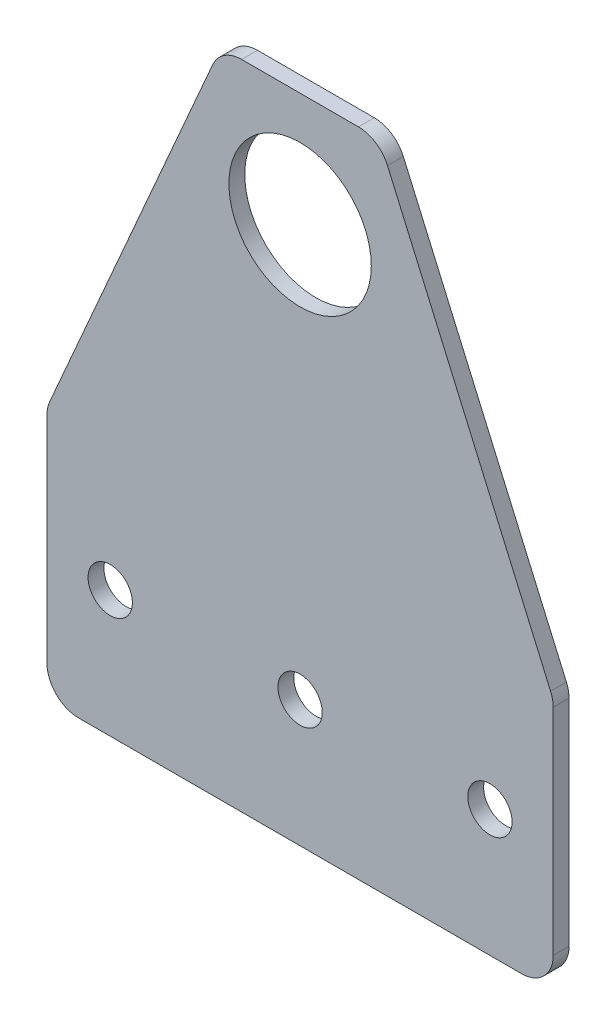
SolidWorks part; units mm, degrees
ref_plane "Plan de face" through (0, 0, 0) normal (0, 0, 1) x (1, 0, 0)
ref_plane "Plan de dessus" through (0, 0, 0) normal (0, 1, 0) x (1, 0, 0)
ref_plane "Plan de droite" through (0, 0, 0) normal (1, 0, 0) x (0, 0, -1)
sketch "Esquisse1" plane through (0, 0, 0) normal (0, 0, 1) x (1, 0, 0)
  line L0 (0, 0) -> (0, 103) construction
  line L1 (-40, 0) -> (40, 0)
  line L2 (40, 0) -> (40, 40)
  line L3 (40, 40) -> (12.5, 103)
  line L4 (12.5, 103) -> (-12.5, 103)
  line L5 (-40, 40) -> (-12.5, 103)
  line L6 (-40, 0) -> (-40, 40)
  line L7 (-40, 20) -> (40, 20) construction
  circle A0 centre (0, 85) radius 11.25
  circle A1 centre (0, 20) radius 3.5
  circle A2 centre (30, 20) radius 3.5
  circle A3 centre (-30, 20) radius 3.5
  dimension "D5" = 22.5
  dimension "D6" = 18
  dimension "D8" = 7
  dimension "D9" = 30
  dimension "D1" = 80
  dimension "D2" = 40
  dimension "D3" = 25
  dimension "D4" = 45
  dimension "D7" = 20
extrude "Boss.-Extru.1" add sketch "Esquisse1" along normal blind 2.5
fillet "Congé1" radius 5 6 edges at (12.5, 103, 1.25) (-12.5, 103, 1.25) (-40, 40, 1.25) (40, 40, 1.25) (40, 0, 1.25) (-40, 0, 1.25)
